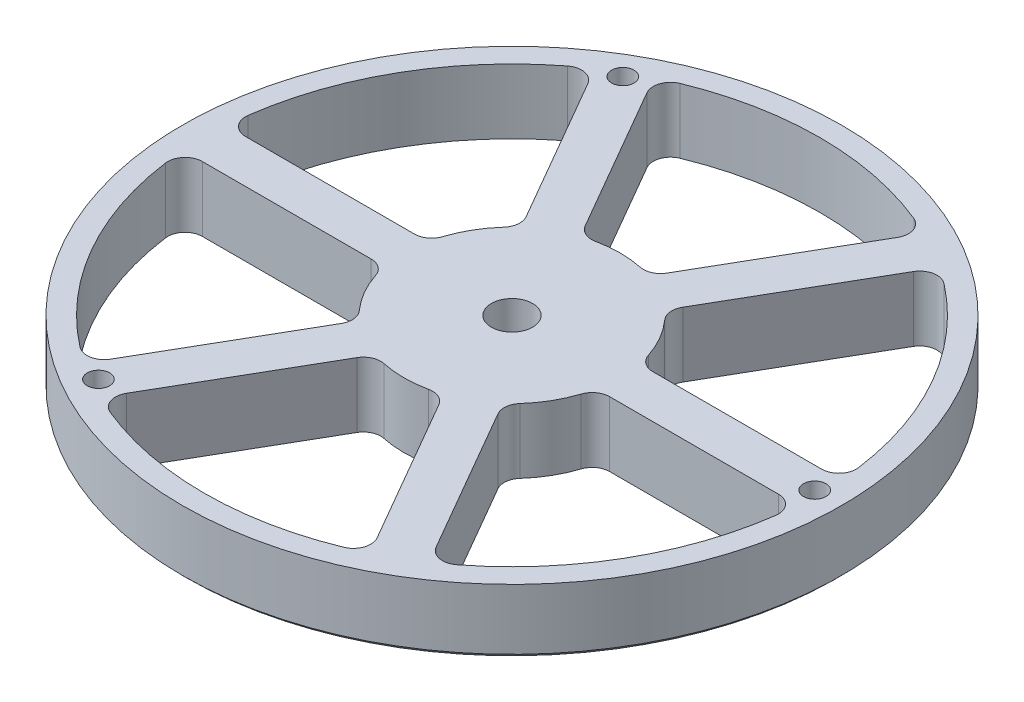
SolidWorks part; units mm, degrees
material "6061-T6 (SS)"
ref_plane "Front Plane" through (0, 0, 0) normal (0, 0, 1) x (1, 0, 0)
ref_plane "Top Plane" through (0, 0, 0) normal (0, 1, 0) x (1, 0, 0)
ref_plane "Right Plane" through (0, 0, 0) normal (1, 0, 0) x (0, 0, -1)
sketch "Sketch2" plane through (0, 0, 0) normal (1, 0, 0) x (0, 0, -1)
  line L0 (0, 0) -> (-76.2, 0)
  line L1 (-76.2, 0) -> (-76.2, 15)
  line L2 (-76.2, 15) -> (0, 15)
  line L5 (0, 15) -> (0, 0)
  dimension "D1" = 76.2
  dimension "D2" = 15
ref_axis "Axis1" through (0, -0.75, 0) along (0, 1, 0)
revolve "Revolve1" add sketch "Sketch2" angle 360 about axis through (0, -0.75, 0) along (0, 1, 0)
hole_wizard "#6 (0.204) Diameter Hole1" positions "Sketch6" profile "Sketch7" hole size "#6" standard "ANSI Inch" end condition through all
sketch "Sketch6" plane through (0, 15, 0) normal (0, 1, 0) x (1, 0, 0)
  line L0 (0, 0) -> (-69.8201, 120.932) construction
  line L2 (0, 0) -> (0, 109.0908) construction
  point P0 (-35, 60.6218)
  dimension "D1" = 30
  dimension "D2" = 70
sketch "Sketch7" plane through (-35, 15, -60.6218) normal (1, 0, 0) x (0, 0, 1)
  line L0 (0, 0) -> (0, 15)
  line L1 (0, 15) -> (2.5908, 15)
  line L2 (2.5908, 15) -> (2.5908, 0)
  line L5 (2.5908, 0) -> (0, 0)
  line L11 (0, -6.35) -> (0, 107.95) construction
  dimension "Thru Hole Dia." = 5.1816
  dimension "Thru Hole Depth" = 15
pattern_circular "CirPattern3" count 3 over 360 about axis through (0, -0.75, 0) along (0, 1, 0) of "#6 (0.204) Diameter Hole1"
sketch "Sketch8" plane through (0, 15, 0) normal (0, 1, 0) x (1, 0, 0)
  line L4 (0, 0) -> (0, 93.9995) construction
  line L5 (0, 0) -> (113.8372, 0) construction
  line L6 (-7.9173, 23.7132) -> (-31.182, 64.0088)
  line L7 (7.9173, 23.7132) -> (31.182, 64.0088)
  line L8 (0, 0) -> (-35, 60.6218) construction
  arc A0 (-7.9173, 23.7132) -> (7.9173, 23.7132) centre (0, 0) cw
  arc A1 (-31.182, 64.0088) -> (31.182, 64.0088) centre (0, 0) cw
  circle A2 centre (0, 0) radius 76.2 construction
  dimension "D1" = 25
  dimension "D2" = 5
  dimension "D3" = 5
extrude "Cut-Extrude1" cut sketch "Sketch8" against normal through all
fillet "Fillet1" radius 4 4 edges at (7.9173, 7.5, -23.7132) (31.182, 7.5, -64.0088) (-7.9173, 7.5, -23.7132) (-31.182, 7.5, -64.0088)
pattern_circular "CirPattern4" count 6 over 360 about axis through (0, -0.75, 0) along (0, 1, 0) of "Cut-Extrude1", "Fillet1"
chamfer "Chamfer2" distance 1 angle 45 1 edges at (0, 0, -76.2)
hole_wizard "3/8 (0.375) Diameter Hole1" positions "Sketch9" profile "Sketch11" hole size "3/8" standard "ANSI Inch" end condition through all
sketch "Sketch9" plane through (0, 0, 0) normal (0, -1, 0) x (-1, 0, 0)
  point P0 (0, 0)
sketch "Sketch11" plane through (0, 0, 0) normal (1, 0, 0) x (0, 0, -1)
  line L0 (0, 0) -> (0, 15)
  line L1 (0, 15) -> (4.7625, 15)
  line L2 (4.7625, 15) -> (4.7625, 0)
  line L5 (4.7625, 0) -> (0, 0)
  line L11 (0, -6.35) -> (0, 107.95) construction
  dimension "Thru Hole Dia." = 9.525
  dimension "Thru Hole Depth" = 15
equation "\"TubeDiameter\"= 6.000in"
equation "\"D1@Sketch2\"=\"TubeDiameter\"/2"
